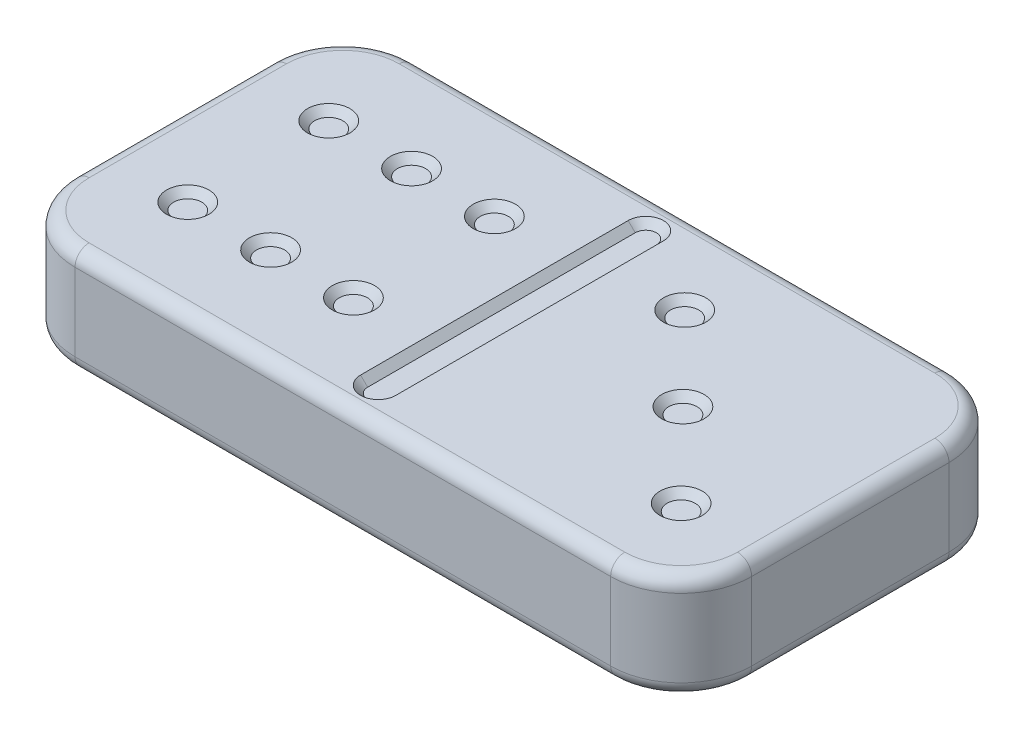
SolidWorks part; units mm, degrees
material "ABS"
ref_plane "Front Plane" through (0, 0, 0) normal (0, 0, 1) x (1, 0, 0)
ref_plane "Top Plane" through (0, 0, 0) normal (0, 1, 0) x (1, 0, 0)
ref_plane "Right Plane" through (0, 0, 0) normal (1, 0, 0) x (0, 0, -1)
sketch "Esquisse1" plane through (0, 0, 0) normal (0, 1, 0) x (1, 0, 0)
  line L1 (0, 0) -> (48, 0)
  line L2 (0, 0) -> (0, 24)
  line L3 (0, 24) -> (48, 24)
  line L4 (48, 0) -> (48, 24)
  dimension "D1" = 48
  dimension "D2" = 24
extrude "Extrusion1" add sketch "Esquisse1" along normal blind 7.5
fillet "Congé2" radius 5 4 edges at (48, 3.75, 0) (48, 3.75, -24) (0, 3.75, 0) (0, 3.75, -24)
fillet "Congé5" radius 1 8 edges at (46.5355, 7.5, -22.5355) (48, 7.5, -12) (46.5355, 7.5, -1.4645) (24, 7.5, 0) (1.4645, 7.5, -1.4645) (0, 7.5, -12) (1.4645, 7.5, -22.5355) (24, 7.5, -24)
fillet "Congé6" radius 1 8 edges at (46.5355, 0, -22.5355) (48, 0, -12) (46.5355, 0, -1.4645) (24, 0, 0) (1.4645, 0, -1.4645) (0, 0, -12) (1.4645, 0, -22.5355) (24, 0, -24)
sketch "Esquisse4" plane through (0, 7.5, 0) normal (0, 1, 0) x (1, 0, 0)
  line L0 (1, 12) -> (47, 12) construction
  line L1 (1, 19) -> (1, 5) construction
  line L2 (47, 5) -> (47, 19) construction
  line L3 (24, 23) -> (24, 1) construction
  line L4 (43, 23) -> (5, 23) construction
  line L5 (5, 1) -> (43, 1) construction
  line L7 (23.75, 21.4914) -> (24.25, 21.4914)
  line L8 (23.75, 21.4914) -> (23.75, 2.5086)
  line L9 (23.75, 2.5086) -> (24.25, 2.5086)
  line L10 (24.25, 21.4914) -> (24.25, 2.5086)
  line L11 (23.75, 21.4914) -> (24.25, 2.5086) construction
  line L12 (23.75, 2.5086) -> (24.25, 21.4914) construction
  point P12 (24, 12)
  dimension "D1" = 0.5
extrude "Extrusion2" cut sketch "Esquisse4" against normal blind 0.5
sketch "Esquisse5" plane through (0, 7.5, 0) normal (0, 1, 0) x (1, 0, 0)
  line L0 (24.25, 21.4914) -> (23.75, 21.4914) construction
  line L1 (23.75, 2.5086) -> (24.25, 2.5086) construction
  circle A0 centre (24, 21.4914) radius 0.25
  circle A1 centre (24, 2.5086) radius 0.25
  dimension "D1" = 0.5
  dimension "D2" = 0.5
extrude "Extrusion3" cut sketch "Esquisse5" against normal blind 0.5
chamfer "Chanfrein1" distance 1 angle 45 4 edges at (24, 7.5, -21.7414) (24.25, 7.5, -12) (24, 7.5, -2.2586) (23.75, 7.5, -12)
sketch "Esquisse6" plane through (0, 7.5, 0) normal (0, 1, 0) x (1, 0, 0)
  line L0 (1, 17) -> (22.75, 17) construction
  line L1 (47, 5) -> (47, 19) construction
  line L2 (25.25, 21.4914) -> (25.25, 2.5086) construction
  line L3 (30.25, 18) -> (42, 6) construction
  line L5 (1, 19) -> (1, 5) construction
  line L6 (1, 12) -> (1, 5) construction
  line L7 (1, 12) -> (1, 19) construction
  line L8 (1, 15.5) -> (1, 19) construction
  line L9 (1, 5) -> (1, 8.5) construction
  line L10 (22.75, 2.5086) -> (22.75, 21.4914) construction
  line L11 (1, 7) -> (22.75, 7) construction
  line L12 (6.4158, 23) -> (6.4158, 17) construction
  line L13 (43, 23) -> (5, 23) construction
  line L14 (6.4158, 7) -> (6.4158, 1) construction
  line L15 (5, 1) -> (43, 1) construction
  line L16 (11.875, 17) -> (6, 17) construction
  line L17 (11.875, 17) -> (11.875, 7) construction
  circle A0 centre (42, 6) radius 1.5
  circle A1 centre (30.25, 18) radius 1.5
  circle A2 centre (11.875, 17) radius 1.5
  circle A3 centre (17.75, 17) radius 1.5
  circle A4 centre (6, 17) radius 1.5
  circle A5 centre (11.875, 7) radius 1.5
  circle A6 centre (6, 7) radius 1.5
  circle A7 centre (17.75, 7) radius 1.5
  circle A9 centre (36.125, 12) radius 1.5
  dimension "D1" = 3
  dimension "D5" = 5
  dimension "D2" = 6
  dimension "D3" = 6
  dimension "D4" = 90
  dimension "D6" = 5
  dimension "D7" = 5
  dimension "D8" = 5
  dimension "D9" = 5
  dimension "D10" = 5
extrude "Extrusion6" cut sketch "Esquisse6" against normal blind 0.5 draft 45
